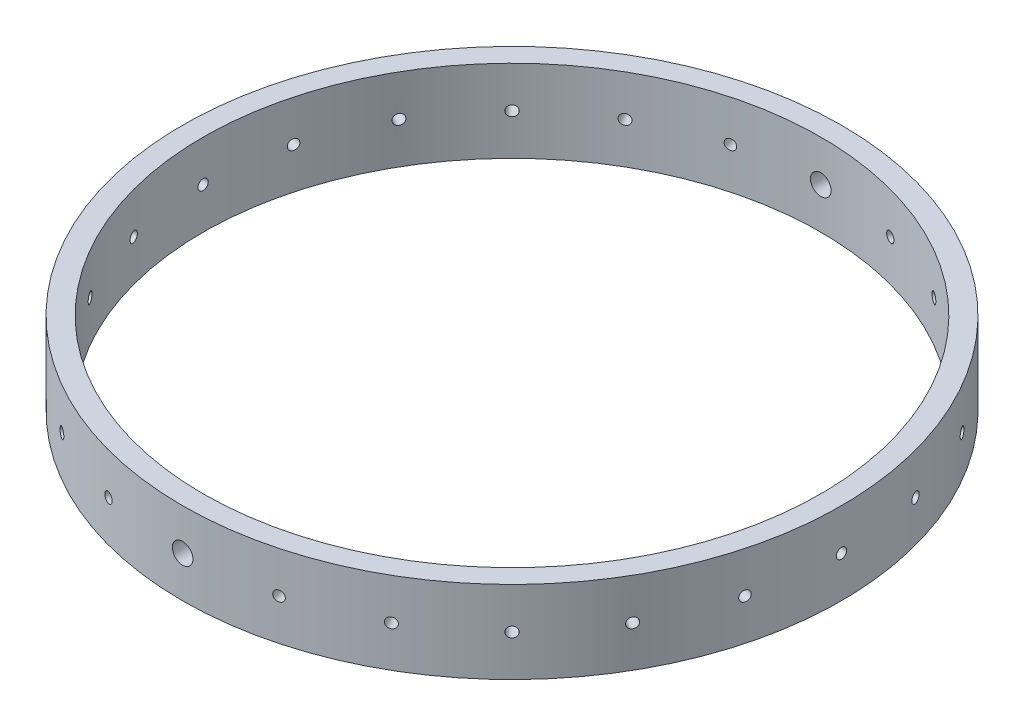
SolidWorks part; units mm, degrees
ref_plane "Front Plane" through (0, 0, 0) normal (0, 0, 1) x (1, 0, 0)
ref_plane "Top Plane" through (0, 0, 0) normal (0, 1, 0) x (1, 0, 0)
ref_plane "Right Plane" through (0, 0, 0) normal (1, 0, 0) x (0, 0, -1)
sketch "Sketch1" plane through (0, 0, 0) normal (0, 1, 0) x (1, 0, 0)
  circle A0 centre (0, 0) radius 101.6
  circle A1 centre (0, 0) radius 95.25
  dimension "D1" = 203.2
  dimension "D2" = 190.5
extrude "Boss-Extrude1" add sketch "Sketch1" along normal blind 25.4
sketch "Sketch2" plane through (0, 0, 0) normal (0, 0, 1) x (1, 0, 0)
  circle A0 centre (0, 12.7) radius 3.175
  dimension "D1" = 6.35
extrude "Cut-Extrude1" cut sketch "Sketch2" against normal through all and the other way through all
sketch "Sketch3" plane through (0, 0, 0) normal (1, 0, 0) x (0, 0, -1)
  circle A0 centre (0, 12.7) radius 1.5875
  dimension "D1" = 3.175
extrude "Cut-Extrude3" cut sketch "Sketch3" against normal through all
sketch "Sketch4" plane through (0, 0, 0) normal (1, 0, 0) x (0, 0, -1)
  line L0 (0, 0) -> (0, 72.5565) construction
pattern_circular "CirPattern1" count 24 over 360 about axis through (0, 0, 0) along (0, 1, 0) of "Cut-Extrude3" reverse direction yes
